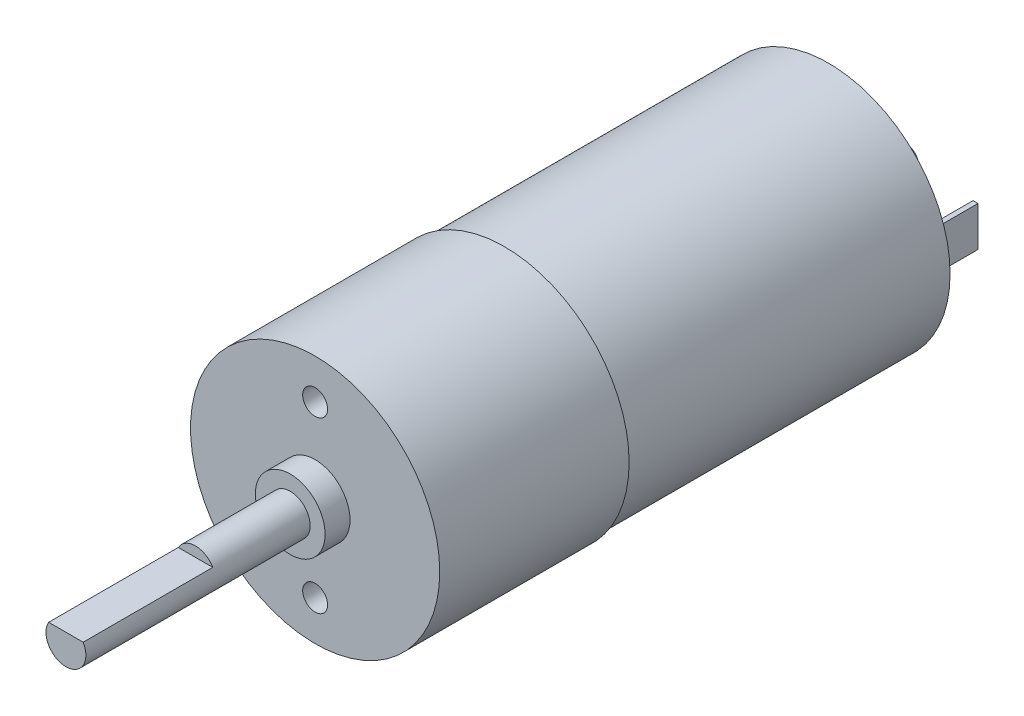
SolidWorks part; units mm, degrees
ref_plane "Front Plane" through (0, 0, 0) normal (0, 0, 1) x (1, 0, 0)
ref_plane "Top Plane" through (0, 0, 0) normal (0, 1, 0) x (1, 0, 0)
ref_plane "Right Plane" through (0, 0, 0) normal (1, 0, 0) x (0, 0, -1)
sketch "스케치1" plane through (0, 0, 0) normal (0, 0, 1) x (1, 0, 0)
  circle A0 centre (0, 0) radius 12.5
extrude "보스-돌출1" add sketch "스케치1" along normal blind 19
sketch "스케치2" plane through (0, 0, 19) normal (0, 0, 1) x (1, 0, 0)
  circle A0 centre (0, 0) radius 3.5
extrude "보스-돌출2" add sketch "스케치2" along normal blind 2.5
sketch "스케치3" plane through (0, 0, 21.5) normal (0, 0, 1) x (1, 0, 0)
  circle A0 centre (0, 0) radius 2
extrude "보스-돌출3" add sketch "스케치3" along normal blind 22.5
sketch "스케치4" plane through (0, 0, 44) normal (0, 0, 1) x (1, 0, 0)
  line L0 (0, 0) -> (50000, 0) construction
  line L1 (-2.3599, 1) -> (49997.6401, 1) construction
  line L3 (3.3297, 1) -> (-3.2328, 1)
  line L4 (3.3297, 1) -> (3.3297, 2.1821)
  line L5 (3.3297, 2.1821) -> (-3.2328, 2.1821)
  line L6 (-3.2328, 1) -> (-3.2328, 2.1821)
  dimension "D1" = 1
extrude "컷-돌출1" cut sketch "스케치4" against normal blind 13
sketch "스케치5" plane through (0, 0, 0) normal (0, 0, -1) x (-1, 0, 0)
  circle A0 centre (0, 0) radius 12.2
extrude "보스-돌출5" add sketch "스케치5" along normal blind 32.5
sketch "스케치6" plane through (0, 0, -32.5) normal (0, 0, -1) x (-1, 0, 0)
  circle A0 centre (0, 0) radius 3.5
extrude "보스-돌출6" add sketch "스케치6" along normal blind 3
sketch "스케치7" plane through (0, 0, -35.5) normal (0, 0, -1) x (-1, 0, 0)
  circle A0 centre (0, 0) radius 1
extrude "보스-돌출7" add sketch "스케치7" along normal blind 5
sketch "스케치8" plane through (0, 0, 19) normal (0, 0, 1) x (1, 0, 0)
  line L0 (0, 0.6304) -> (0, 50000.6304) construction
  circle A0 centre (0, 0) radius 8.5 construction
  circle A1 centre (0, 8.5) radius 1.25
  circle A2 centre (0, -8.5) radius 1.25
  dimension "D1" = 2.5
  dimension "D2" = 2.5
extrude "컷-돌출2" cut sketch "스케치8" against normal blind 5
sketch "스케치9" plane through (0, 0, -32.5) normal (0, 0, -1) x (-1, 0, 0)
  line L0 (0, 0) -> (50000, 0) construction
  line L1 (-9, 2.2495) -> (-9, -49997.7505) construction
  line L2 (9, 2.6702) -> (9, -49997.3298) construction
  line L4 (-9, -2) -> (-9.5, -2)
  line L5 (-9, -2) -> (-9, 2)
  line L6 (-9, 2) -> (-9.5, 2)
  line L7 (-9.5, -2) -> (-9.5, 2)
  line L8 (9, -2) -> (9.5, -2)
  line L9 (9, -2) -> (9, 2)
  line L10 (9, 2) -> (9.5, 2)
  line L11 (9.5, -2) -> (9.5, 2)
  point P17 (6.3762, 5.5185)
  dimension "D1" = 0.5
  dimension "D2" = 9
  dimension "D3" = 9
  dimension "D4" = 0.5
  dimension "D5" = 4
  dimension "D6" = 4
  dimension "D7" = 2
  dimension "D8" = 2
extrude "보스-돌출8" add sketch "스케치9" along normal blind 5.5
